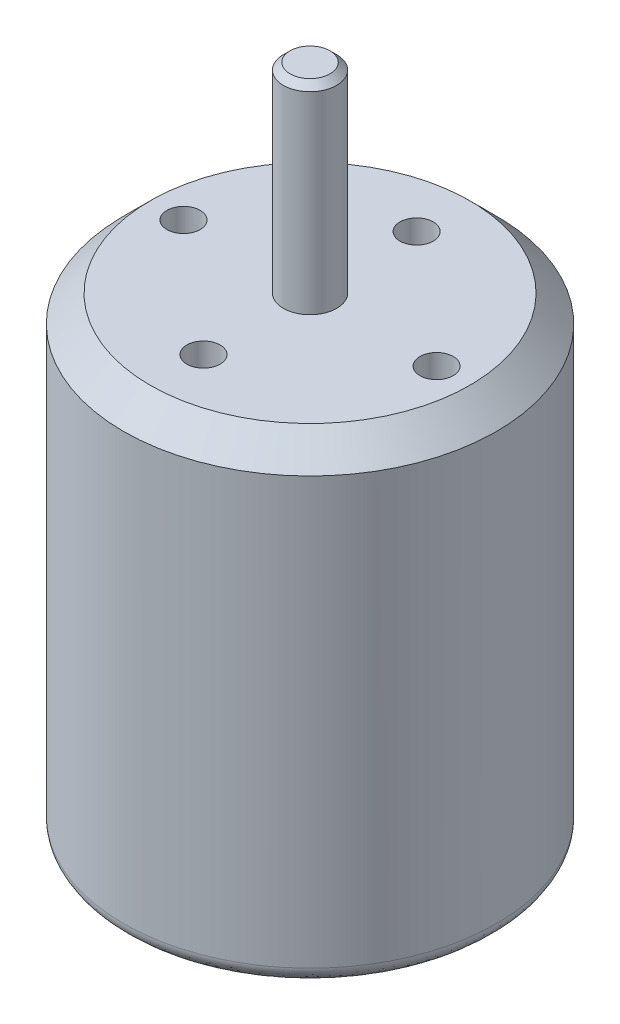
SolidWorks part; units mm, degrees
material "6061-T6 (SS)"
ref_plane "Front Plane" through (0, 0, 0) normal (0, 0, 1) x (1, 0, 0)
ref_plane "Top Plane" through (0, 0, 0) normal (0, 1, 0) x (1, 0, 0)
ref_plane "Right Plane" through (0, 0, 0) normal (1, 0, 0) x (0, 0, -1)
ref_axis "X" through (-88.99, 0, 0) along (1, 0, 0)
ref_axis "Y" through (0, 55, 0) along (0, -1, 0)
ref_axis "Z" through (0, 0, -88.99) along (0, 0, 1)
sketch "Sketch1" plane through (0, 0, 0) normal (0, 1, 0) x (1, 0, 0)
  circle A0 centre (0, 0) radius 14
  circle A1 centre (0, 0) radius 2
  dimension "D1" = 28
  dimension "D2" = 4
extrude "Boss-Extrude1" add sketch "Sketch1" against normal blind 36 contours A0
extrude "Boss-Extrude2" add sketch "Sketch1<3>" along normal blind 15 contours A1 region at (0, 0, 0)
sketch "Sketch1<3>" plane through (0, 0, 0) normal (0, 1, 0) x (1, 0, 0) same geometry as "Sketch1"
extrude "Boss-Extrude3" add sketch "Sketch1<4>" against normal blind 2 from surface contours A1 region at (0, 0, 0) starting at face at (0, -36, 14)
sketch "Sketch1<4>" plane through (0, 0, 0) normal (0, 1, 0) x (1, 0, 0) same geometry as "Sketch1"
chamfer "Chamfer1" distance 0.5 angle 45 2 edges at (0, -38, 2) (0, 15, 2)
chamfer "Chamfer2" distance 2 angle 45 1 edges at (0, 0, 14)
fillet "Fillet1" radius 2 1 edges at (0, -36, 14) second distance 4 first distance on face at (0, -2, 14)
sketch "Sketch2" plane through (0, 0, 0) normal (0, 1, 0) x (1, 0, 0)
  line L0 (-9.5, 0) -> (9.5, 0) construction
  line L1 (0, 8) -> (0, -8) construction
  point P1 (9.5, 0)
  point P8 (0, 8)
  point P18 (0, -8)
  point P20 (-9.5, 0)
  point P22 (0, 8)
  point P24 (9.5, 0)
  dimension "D1" = 16
  dimension "D2" = 19
hole_wizard "M3x0.5 Tapped Hole2" positions "Sketch2" profile "Sketch4" tap size "M3x0.5" standard "ANSI Metric"
sketch "Sketch4" plane through (9.5, 0, 0) normal (1, 0, 0) x (0, 0, 1)
  line L0 (0, 0) -> (0, 4.7511)
  line L1 (0, 4.7511) -> (1.25, 4)
  line L2 (1.25, 4) -> (1.25, 0)
  line L5 (1.25, 0) -> (0, 0)
  line L10 (0, 4.7511) -> (-1.25, 4) construction
  line L11 (0, -6.35) -> (0, 107.95) construction
  dimension "Tap Drill Dia." = 2.5
  dimension "Tap Drill Depth" = 4
  dimension "Drill Angle" = 118
cosmetic thread "Hole Thread5" parameters "D1"=6, "D2"=3
cosmetic thread "Hole Thread6" parameters "D1"=6, "D2"=3
cosmetic thread "Hole Thread7" parameters "D1"=6, "D2"=3
cosmetic thread "Hole Thread8" parameters "D1"=6, "D2"=3
sketch "Sketch5" plane through (0, -36, 0) normal (0, -1, 0) x (1, 0, 0)
  line L0 (0, 0) -> (5.1962, 3) construction
  line L1 (0, 0) -> (0, -6) construction
  line L2 (0, 0) -> (-5.1962, 3) construction
  circle A0 centre (0, 0) radius 6 construction
  point P8 (-6, 0)
  point P10 (6, 0)
  dimension "D1" = 12
  dimension "D2" = 120
  dimension "D3" = 120
hole_wizard "M3x0.5 Tapped Hole3" positions "Sketch5" profile "Sketch6" tap size "M3x0.5" standard "ANSI Metric"
sketch "Sketch6" plane through (6, -36, 0) normal (1, 0, 0) x (0, 0, -1)
  line L0 (0, 0) -> (0, 4.7511)
  line L1 (0, 4.7511) -> (1.25, 4)
  line L2 (1.25, 4) -> (1.25, 0)
  line L5 (1.25, 0) -> (0, 0)
  line L10 (0, 4.7511) -> (-1.25, 4) construction
  line L11 (0, -6.35) -> (0, 107.95) construction
  dimension "Tap Drill Dia." = 2.5
  dimension "Tap Drill Depth" = 4
  dimension "Drill Angle" = 118
cosmetic thread "Hole Thread9" parameters "D1"=6, "D2"=3
cosmetic thread "Hole Thread10" parameters "D1"=6, "D2"=3
sketch "Sketch9" plane through (0, -36, 0) normal (0, -1, 0) x (-1, 0, 0)
  point P0 (0, 6)
  point P2 (5.1962, -3)
  point P4 (-5.1962, -3)
hole_wizard "M2.5x0.45 Tapped Hole1" positions "Sketch9" profile "Sketch8" tap size "M2.5x0.45" standard "ANSI Metric"
sketch "Sketch8" plane through (0, -36, -6) normal (1, 0, 0) x (0, 0, -1)
  line L0 (0, 0) -> (0, 4.6159)
  line L1 (0, 4.6159) -> (1.025, 4)
  line L2 (1.025, 4) -> (1.025, 0)
  line L5 (1.025, 0) -> (0, 0)
  line L10 (0, 4.6159) -> (-1.025, 4) construction
  line L11 (0, -6.35) -> (0, 107.95) construction
  dimension "Tap Drill Dia." = 2.05
  dimension "Tap Drill Depth" = 4
  dimension "Drill Angle" = 118
cosmetic thread "Hole Thread11" parameters "D1"=5, "D2"=2.5
cosmetic thread "Hole Thread12" parameters "D1"=5, "D2"=2.5
cosmetic thread "Hole Thread13" parameters "D1"=5, "D2"=2.5
